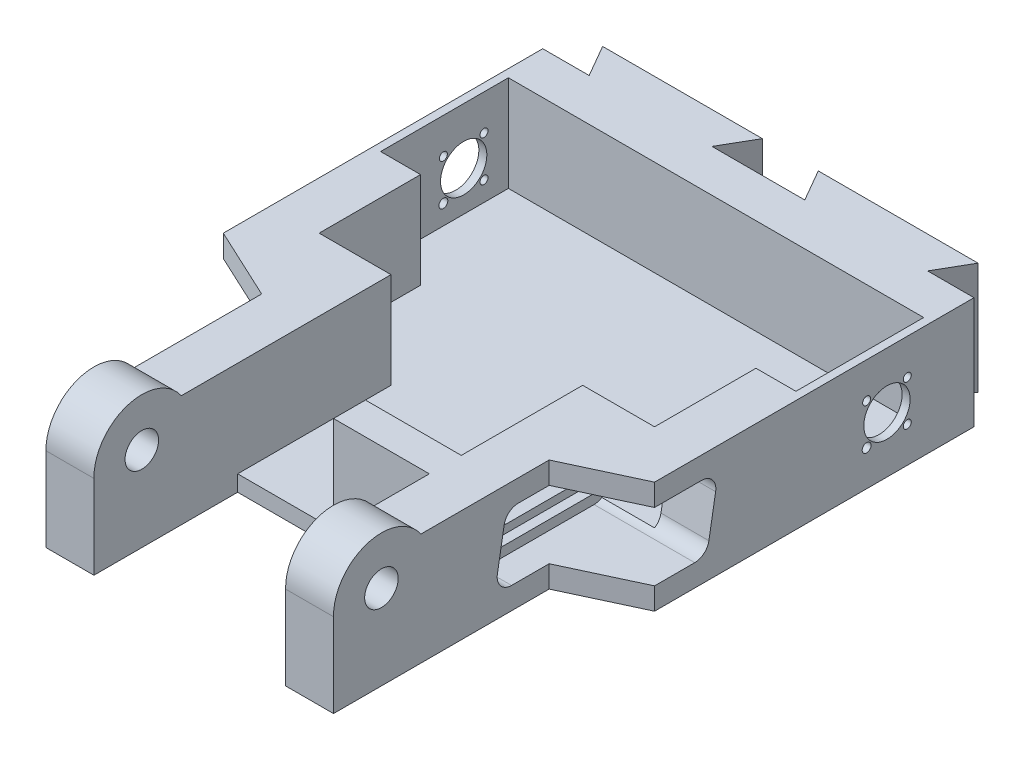
SolidWorks part; units mm, degrees
other "Markup1"
sketch "Sketch19"
material "Nylon 101"
ref_plane "Front Plane" through (0, 0, 0) normal (0, 0, 1) x (1, 0, 0)
ref_plane "Top Plane" through (0, 0, 0) normal (0, 1, 0) x (1, 0, 0)
ref_plane "Right Plane" through (0, 0, 0) normal (1, 0, 0) x (0, 0, -1)
sketch "Sketch1" plane through (0, 0, 0) normal (0, 1, 0) x (1, 0, 0)
  line L0 (-92.7281, 0) -> (108.2186, 0) construction
  line L1 (0, -93) -> (0, 105.5293) construction
  line L2 (30, -5) -> (-15, -5) construction
  line L3 (-30, 0) -> (30, 0)
  line L4 (-30, 0) -> (-30, -38)
  line L6 (30, 0) -> (30, -38)
  line L7 (-15, -5) -> (-15, -33) construction
  line L8 (-15, -33) -> (30, -33) construction
  line L9 (-30, -48) -> (30, -48)
  line L10 (-30.0789, -53) -> (30, -53) construction
  line L13 (-30, -38) -> (30, -38)
  line L14 (-67.5, -15) -> (-67.5, 85)
  line L15 (-52.5, 0) -> (52.5, 0)
  line L16 (-52.5, 0) -> (-52.5, 70)
  line L17 (-52.5, 70) -> (52.5, 70)
  line L18 (52.5, 0) -> (52.5, 70)
  line L19 (-67.5, 85) -> (67.5, 85)
  line L20 (67.5, -15) -> (67.5, 85)
  line L22 (-45, -25.4919) -> (-45, -78)
  line L26 (-30, -78) -> (-45, -78)
  line L27 (30, -78) -> (45, -78)
  line L29 (-45, 15) -> (-45, -93) construction
  line L30 (-45, -93) -> (45, -93) construction
  line L31 (45, 15) -> (45, -93) construction
  line L32 (-67.5, -15) -> (67.5, -15) construction
  line L33 (45, -25.4919) -> (45, -78)
  line L34 (-30, -48) -> (-30, -78)
  line L35 (30, -48) -> (30, -78)
  line L36 (-30, 0) -> (-30, -78) construction
  line L37 (-67.5, -15) -> (-45, -25.4919)
  line L38 (30, 0) -> (30, -78) construction
  line L39 (-30, -78) -> (30, -78) construction
  line L40 (67.5, -15) -> (45, -25.4919)
  line L41 (-45, 15) -> (45, 15) construction
  point P1 (-30, -93)
  point P17 (0, 0)
  point P18 (30, -78)
  point P35 (30, -53)
  point P38 (0, 0)
  dimension "D1" = 60
  dimension "D2" = 45
  dimension "D3" = 28
  dimension "D4" = 5
  dimension "D5" = 10
  dimension "D6" = 25
  dimension "D7" = 5
  dimension "D9" = 30
  dimension "D10" = 65
  dimension "D11" = 5
  dimension "D12" = 105
  dimension "D13" = 52.5
  dimension "D14" = 70
  dimension "D16" = 65
  dimension "D15" = 15
extrude "Boss-Extrude1" add sketch "Sketch1" along normal blind 30 contours L40 L20 L19 L14 L37 L22 L26 L34 L9 L35 L27 L33 L18 L15 L6 L13 L4 L16 L17 region at (-32.1165, 0, 63)
sketch "Sketch2" plane through (0, 0, 0) normal (0, -1, 0) x (1, 0, 0)
  line L26 (67.5, 15) -> (45, 25.4919)
  line L27 (45, 25.4919) -> (45, 78)
  line L28 (45, 78) -> (30, 78)
  line L29 (30, 78) -> (30, 48)
  line L30 (30, 48) -> (-30, 48)
  line L31 (-30, 48) -> (-30, 78)
  line L32 (-30, 78) -> (-45, 78)
  line L33 (-45, 78) -> (-45, 25.4919)
  line L34 (-45, 25.4919) -> (-67.5, 15)
  line L35 (-67.5, 15) -> (-67.5, -85)
  line L36 (-67.5, -85) -> (67.5, -85)
  line L37 (67.5, -85) -> (67.5, 15)
  line L38 (67.5, 15) -> (45, 25.4919)
  line L39 (45, 25.4919) -> (45, 78)
  line L40 (45, 78) -> (30, 78)
  line L41 (30, 78) -> (30, 48)
  line L42 (30, 48) -> (-30, 48)
  line L43 (-30, 48) -> (-30, 78)
  line L44 (-30, 78) -> (-45, 78)
  line L45 (-45, 78) -> (-45, 25.4919)
  line L46 (-45, 25.4919) -> (-67.5, 15)
  line L47 (-67.5, 15) -> (-67.5, -85)
  line L48 (-67.5, -85) -> (67.5, -85)
  line L49 (67.5, -85) -> (67.5, 15)
  dimension "D1" = 0
extrude "Boss-Extrude2" add sketch "Sketch2" along normal blind 5
sketch "Sketch3" plane through (-45, 0, 0) normal (-1, 0, 0) x (0, 0, 1)
  line L0 (78, 30) -> (78, -5)
  line L1 (78, -5) -> (138, -5) construction
  line L2 (138, -5) -> (92.9979, 21.2512) construction
  line L3 (138, -5) -> (138, 48) construction
  line L4 (138, 21.5) -> (78, 21.5) construction
  line L5 (78, 30) -> (65.6408, 30)
  line L6 (25.4919, 30) -> (78, 30) construction
  line L7 (92.9979, 21.2512) -> (92.9979, -5)
  line L8 (78, -5) -> (92.9979, -5)
  circle A0 centre (78, 21.5) radius 5
  arc A1 (92.9979, 21.2512) -> (65.6408, 30) centre (78, 21.5) ccw
  line M9 (78, -5) -> (78, 30)
  line M10 (78, 30) -> (25.4919, 30)
  dimension "D3" = 10
  dimension "D4" = 10
  dimension "D1" = 60
  dimension "D2" = 53
  dimension "D5" = 14.9979
extrude "Boss-Extrude3" add sketch "Sketch3" against normal blind 15 contours L2 A1 A0 L1 M10 M9 region at (-45, 15.5608, 84.3436)
extrude "Boss-Extrude6" add sketch "Sketch3<3>" along normal up to surface (-75 mm away) from surface contours L7 A1 A0 L8 M10 M9 region at (-45, 15.5608, 84.3436) up to face at (30, 12.5, 63) starting at face at (45, 12.5, 51.746)
sketch "Sketch3<3>" plane through (-45, 0, 0) normal (-1, 0, 0) x (0, 0, 1) same geometry as "Sketch3"
sketch "Sketch5" plane through (45, 0, 0) normal (1, 0, 0) x (0, 0, -1)
  line L0 (-78, 26.5) -> (-78, 16.5) construction
  circle A0 centre (-78, 21.5) radius 5.25
  dimension "D1" = 10.5
extrude "Cut-Extrude1" cut sketch "Sketch5" against normal blind 100
sketch "Sketch6" plane through (0, 0, 48) normal (0, 0, 1) x (1, 0, 0)
  line L1 (-30, 30) -> (0, 30)
  line L2 (-30, 30) -> (-30, 0)
  line L3 (-30, 0) -> (0, 0)
  line L4 (0, 30) -> (0, 0)
extrude "Cut-Extrude2" cut sketch "Sketch6" against normal blind 13
sketch "Sketch11" plane through (52.5, 0, 0) normal (-1, 0, 0) x (0, 0, 1)
  line L0 (-57.75, 30) -> (-57.75, 0) construction
  line L1 (15, 30) -> (-85, 30) construction
  line L2 (-64.114, 18.864) -> (-57.75, 12.5)
  line L3 (-57.75, 12.5) -> (-51.386, 6.136)
  line L4 (-64.114, 6.136) -> (-57.75, 12.5)
  line L5 (-57.75, 12.5) -> (-51.386, 18.864)
  line L6 (-65, 12.5) -> (-85, 12.5) construction
  line L7 (-85, 30) -> (-85, -5) construction
  circle A0 centre (-57.75, 12.5) radius 7.25
  circle A1 centre (-51.386, 18.864) radius 1.25
  circle A2 centre (-64.114, 18.864) radius 1.25
  circle A3 centre (-64.114, 6.136) radius 1.25
  circle A4 centre (-51.386, 6.136) radius 1.3965
  dimension "D2" = 14.5
  dimension "D8" = 2.5
  dimension "D9" = 2.5
  dimension "D10" = 2.5
  dimension "D1" = 30
  dimension "D3" = 17.5
  dimension "D4" = 9
  dimension "D5" = 9
  dimension "D6" = 9
  dimension "D7" = 9
  dimension "D11" = 45
  dimension "D12" = 45
  dimension "D13" = 20
extrude "Cut-Extrude5" cut sketch "Sketch11" along normal through all both and the other way through all contours L3 A0 L5 | A2 | L2 A0 L4 | L5 A0 L2 | L4 A0 L3 | A3 | A4 | A1 region at (52.5, 19.9861, -51.8509) region at (52.5, 7.3898, -50.8667) region at (52.5, 6.6009, -62.9918) region at (52.5, 16.8515, -57.75) region at (52.5, 12.5, -62.1015) region at (52.5, 19.3288, -65.2361) region at (52.5, 12.5, -53.3985) region at (52.5, 8.1485, -57.75)
sketch "Sketch12" plane through (0, 0, 0) normal (1, 0, 0) x (0, 0, -1)
  line L0 (40.0628, 12.5) -> (72.6439, 12.5) construction
  line L1 (57.75, 27.3414) -> (57.75, 3.0865) construction
  line L2 (-15, 30) -> (85, 30) construction
  line L3 (31.75, 30) -> (71.75, 30)
  line L4 (31.75, 30) -> (31.75, 0)
  line L5 (31.75, 0) -> (71.75, 0)
  line L6 (71.75, 30) -> (71.75, 0)
  dimension "D1" = 40
  dimension "D2" = 14
  dimension "D3" = 30
extrude "Cut-Extrude6" cut sketch "Sketch12" against normal blind 65 and the other way blind 65
sketch "Sketch17" plane through (0, 30, 0) normal (0, 1, 0) x (1, 0, 0)
  line L0 (-33.75, 85) -> (-33.75, 95) construction
  line L1 (-67.5, 85) -> (67.5, 85) construction
  line L2 (-67.5, 19) -> (-67.5, 85) construction
  line L3 (0, 73.8727) -> (0, 101.7889) construction
  line L4 (-52.9765, 85) -> (-58.75, 95)
  line L5 (-58.75, 95) -> (-8.75, 95)
  line L6 (-8.75, 95) -> (-14.5235, 85)
  line L7 (-52.9765, 85) -> (-14.5235, 85)
  line L8 (52.9765, 85) -> (58.75, 95)
  line L9 (58.75, 95) -> (8.75, 95)
  line L10 (8.75, 95) -> (14.5235, 85)
  line L11 (52.9765, 85) -> (14.5235, 85)
  dimension "D1" = 33.75
  dimension "D2" = 10
  dimension "D3" = 60
  dimension "D4" = 60
  dimension "D5" = 50
  dimension "D6" = 25
extrude "Boss-Extrude5" add sketch "Sketch17" against normal blind 35 contours L8 L9 L10 L11 | L7 L6 L5 L4
sketch "Sketch20" plane through (0, 0, 0) normal (1, 0, 0) x (0, 0, -1)
  line L0 (-30, 12.5) -> (-7.5803, 12.5) construction
  line L1 (-30, 14.625) -> (-7.5803, 14.625)
  line L2 (-30, 10.375) -> (-7.5803, 10.375)
  line L3 (-22.7333, 18.6193) -> (-37.2667, 6.3807) construction
  line L4 (-35.1531, 18.6193) -> (-24.8469, 6.3807) construction
  line L5 (-14.8469, 6.3807) -> (-0.3136, 18.6193) construction
  line L6 (-12.7333, 18.6193) -> (-2.4272, 6.3807) construction
  line L7 (-35.1531, 18.6193) -> (-0.3136, 18.6193) construction
  line L8 (-35.1531, 20.1193) -> (-0.3136, 20.1193)
  line L9 (-35.1531, 17.1193) -> (-0.3136, 17.1193)
  line L10 (-37.2667, 6.3807) -> (-2.4272, 6.3807) construction
  line L11 (-37.2667, 7.8807) -> (-2.4272, 7.8807)
  line L12 (-37.2667, 4.8807) -> (-2.4272, 4.8807)
  line L13 (-18.7901, 30) -> (-18.7901, -5) construction
  line L14 (-25.4919, 30) -> (-65.6408, 30) construction
  line L15 (-25.4919, -5) -> (-92.9979, -5) construction
  line L16 (-44, 12.5) -> (-48, 12.5) construction
  line L17 (-30, 28.5) -> (-7.5803, 28.5)
  line L18 (-30, -3.5) -> (-7.5803, -3.5)
  line L20 (-35.1531, 23.1193) -> (-0.3136, 23.1193) construction
  line L21 (-35.1531, 14.1193) -> (-0.3136, 14.1193) construction
  line L22 (-37.2667, 10.8807) -> (-2.4272, 10.8807) construction
  line L23 (-37.2667, 1.8807) -> (-2.4272, 1.8807) construction
  line L24 (-35.1531, 23.1193) -> (-0.3136, 23.1193)
  line L25 (-37.2667, 1.8807) -> (-2.4272, 1.8807)
  line L26 (2.0072, 5.6149) -> (4.1208, 17.8535)
  line L28 (-48, 30) -> (-48, -5) construction
  line L29 (-39.5874, 19.3851) -> (-41.701, 7.1465)
  arc A0 (-30, 14.625) -> (-30, 10.375) centre (-30, 12.5) ccw
  arc A1 (-7.5803, 10.375) -> (-7.5803, 14.625) centre (-7.5803, 12.5) ccw
  arc A2 (-35.1531, 20.1193) -> (-35.1531, 17.1193) centre (-35.1531, 18.6193) ccw
  arc A3 (-0.3136, 17.1193) -> (-0.3136, 20.1193) centre (-0.3136, 18.6193) ccw
  arc A4 (-37.2667, 7.8807) -> (-37.2667, 4.8807) centre (-37.2667, 6.3807) ccw
  arc A5 (-2.4272, 4.8807) -> (-2.4272, 7.8807) centre (-2.4272, 6.3807) ccw
  circle A6 centre (-30, 12.5) radius 14 construction
  arc A7 (-0.3136, 14.1193) -> (-0.3136, 23.1193) centre (-0.3136, 18.6193) ccw construction
  arc A8 (-35.1531, 23.1193) -> (-35.1531, 14.1193) centre (-35.1531, 18.6193) ccw construction
  arc A9 (-2.4272, 1.8807) -> (-2.4272, 10.8807) centre (-2.4272, 6.3807) ccw construction
  arc A10 (-37.2667, 10.8807) -> (-37.2667, 1.8807) centre (-37.2667, 6.3807) ccw construction
  arc A11 (-2.4272, 1.8807) -> (2.0072, 5.6149) centre (-2.4272, 6.3807) ccw
  arc A12 (4.1208, 17.8535) -> (-0.3136, 23.1193) centre (-0.3136, 18.6193) ccw
  arc A13 (-35.1531, 23.1193) -> (-39.5874, 19.3851) centre (-35.1531, 18.6193) ccw
  arc A14 (-41.701, 7.1465) -> (-37.2667, 1.8807) centre (-37.2667, 6.3807) ccw
  circle A15 centre (-7.5803, 12.5) radius 14 construction
  circle A16 centre (-30, 12.5) radius 16 construction
  circle A17 centre (-7.5803, 12.5) radius 16 construction
  arc A18 (-7.5803, -3.5) -> (-7.5803, 28.5) centre (-7.5803, 12.5) ccw
  arc A19 (-30, 28.5) -> (-30, -3.5) centre (-30, 12.5) ccw
  point P2 (-18.7901, 12.5)
  point P7 (-17.7333, 18.6193)
  point P10 (-30, 12.5)
  point P13 (-30, 12.5)
  point P16 (-7.5803, 12.5)
  point P19 (-7.5803, 12.5)
  point P24 (-19.8469, 6.3807)
  dimension "D6" = 28
  dimension "D8" = 2
  dimension "D1" = 4.25
  dimension "D2" = 19
  dimension "D3" = 16
  dimension "D4" = 10
  dimension "D5" = 3
  dimension "D7" = 4
  dimension "D10" = 3
extrude "Boss-Extrude7" add sketch "Sketch20" along normal blind 6 from surface contours L26 A12 L24 A6 L8 A3 L9 L1 A1 L2 L11 A5 L12 L25 A11 | L8 A6 | L1 A6 L9 | L11 A6 L2 | A6 L12 region at (0, 22.6131, 17.7333) starting at face at (30, 15, 19)
extrude "Cut-Extrude7" cut sketch "Sketch20<3>" along normal through all contours L8 A3 L9 A2 | L1 A1 L2 A0 | L11 A5 L12 A4
sketch "Sketch20<3>" plane through (0, 0, 0) normal (1, 0, 0) x (0, 0, -1) same geometry as "Sketch20"
extrude "Cut-Extrude9" cut sketch "Sketch20<6>" against normal up to surface (-36 mm away) from surface contours L26 A12 L24 A6 L8 A3 L9 L1 A1 L2 L11 A5 L12 L25 A11 | L29 A14 L25 A6 L12 A4 L11 L2 A0 L1 L9 A2 L8 L24 A13 region at (0, 22.6131, 17.7333) up to face at (36, 14.5184, -1.4666) starting at face at (67.5, 18.864, -62.864)
sketch "Sketch20<6>" plane through (0, 0, 0) normal (1, 0, 0) x (0, 0, -1) same geometry as "Sketch20"
extrude "Cut-Extrude10" cut sketch "Sketch20<7>" along normal up to surface (30 mm away) contours L18 A18 L17 A19 up to face at (30, 12.5, 18.7901)
sketch "Sketch20<7>" plane through (0, 0, 0) normal (1, 0, 0) x (0, 0, -1) same geometry as "Sketch20"
extrude "Cut-Extrude11" cut sketch "Sketch20<8>" along normal offset from surface (32.5 mm away) 5 from surface contours L26 A12 L24 A13 L29 A14 L25 A11 up to face at (-30, 11.6304, 50.1266) starting at face at (-67.5, 6.136, -62.864)
sketch "Sketch20<8>" plane through (0, 0, 0) normal (1, 0, 0) x (0, 0, -1) same geometry as "Sketch20"
